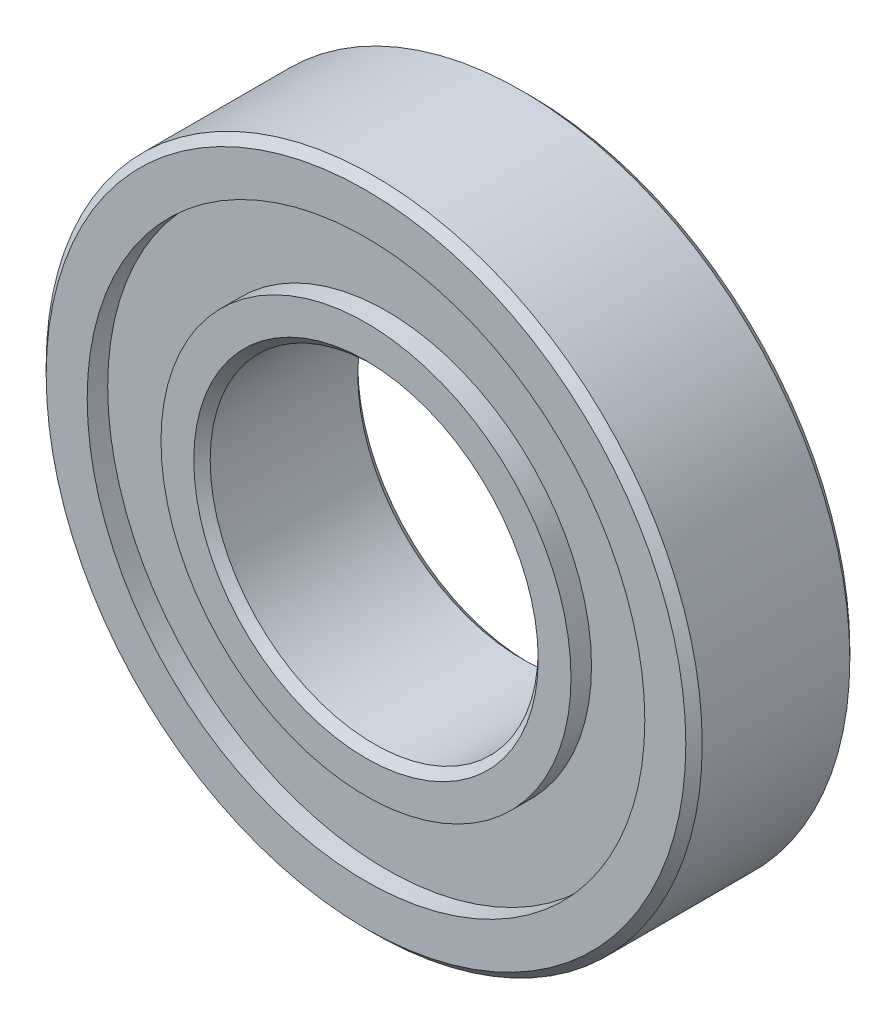
SolidWorks part; units mm, degrees
material "Alloy Steel"
ref_plane "Ebene vorne" through (0, 0, 0) normal (0, 0, 1) x (1, 0, 0)
ref_plane "Ebene oben" through (0, 0, 0) normal (0, 1, 0) x (1, 0, 0)
ref_plane "Ebene rechts" through (0, 0, 0) normal (1, 0, 0) x (0, 0, -1)
sketch "Skizze2" plane through (0, 0, 0) normal (1, 0, 0) x (0, 0, -1)
  line L0 (-11.8458, 0) -> (13.4965, 0) construction
  line L1 (0, 16.288) -> (0, -14.1034) construction
  line L2 (-1, 2) -> (1, 2)
  line L3 (1, 2) -> (1, 2.5)
  line L4 (1, 2.5) -> (0.75, 2.5)
  line L5 (0.75, 2.5) -> (0.75, 3.4)
  line L6 (0.75, 3.4) -> (1, 3.4)
  line L7 (1, 3.4) -> (1, 4)
  line L8 (1, 4) -> (-1, 4)
  line L9 (-1, 3.4) -> (-1, 4)
  line L10 (-0.75, 3.4) -> (-1, 3.4)
  line L11 (-0.75, 2.5) -> (-0.75, 3.4)
  line L12 (-1, 2.5) -> (-0.75, 2.5)
  line L13 (-1, 2) -> (-1, 2.5)
  point P5 (0, 4)
  point P19 (0, 2)
  dimension "D1" = 4
  dimension "D2" = 8
  dimension "D3" = 2
  dimension "D4" = 5
  dimension "D5" = 6.8
  dimension "D6" = 1.5
revolve "Rotation1" add sketch "Skizze2" angle 360 about L0
ref_axis "Achse1" through (0, 0, -14.7636) along (0, 0, 1)
chamfer "Fase1" distance 0.1 angle 45 4 edges at (2, 0, -1) (2, 0, 1) (4, 0, -1) (4, 0, 1)
